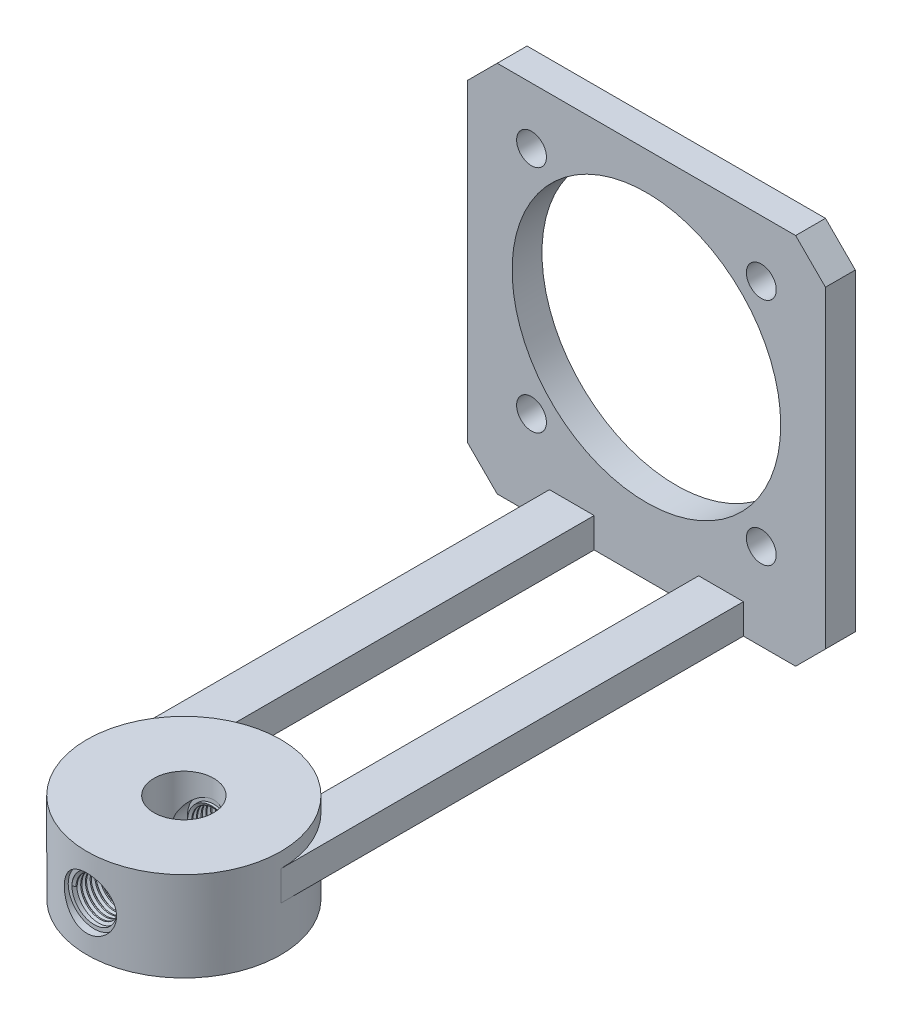
SolidWorks part; units mm, degrees
material "3.0205 (EN-AW 1200)"
ref_plane "前视基准面" through (0, 0, 0) normal (0, 0, 1) x (1, 0, 0)
ref_plane "上视基准面" through (0, 0, 0) normal (0, 1, 0) x (1, 0, 0)
ref_plane "右视基准面" through (0, 0, 0) normal (1, 0, 0) x (0, 0, -1)
sketch "草图1" plane through (0, 0, 0) normal (0, 1, 0) x (1, 0, 0)
  line L1 (5, 0) -> (2.5, 4.3301)
  line L2 (2.5, 4.3301) -> (-2.5, 4.3301)
  line L3 (-2.5, 4.3301) -> (-5, 0)
  line L4 (-5, 0) -> (-2.5, -4.3301)
  line L5 (-2.5, -4.3301) -> (2.5, -4.3301)
  line L6 (5, 0) -> (2.5, -4.3301)
sketch "草图2" plane through (0, 0, 0) normal (0, 1, 0) x (1, 0, 0)
  circle A0 centre (0, 0) radius 6.5
extrude "凸台-拉伸1" add sketch "草图2" along normal blind 2
sketch "草图3" plane through (0, 2, 0) normal (0, 1, 0) x (1, 0, 0)
  circle A0 centre (0, 0) radius 2
extrude "切除-拉伸2" cut sketch "草图3" against normal mid plane 10
sketch "草图4" plane through (0, 2, 0) normal (0, 1, 0) x (1, 0, 0)
  line L1 (6.5, 31) -> (3.8991, 31)
  line L3 (-6.5, 0) -> (-6.5, 31)
  line L4 (-6.5, 31) -> (-4.1009, 31)
  line L7 (-6.5, 0) -> (6.5, 0)
  line L8 (6.5, 0) -> (6.5, 31)
  line L11 (-4.1009, 31) -> (3.8991, 31)
  circle A0 centre (0, 0) radius 6.5 construction
  circle A1 centre (0, 0) radius 6.5
extrude "凸台-拉伸2" add sketch "草图4" against normal blind 2
sketch "草图6" plane through (0, 0, -31) normal (0, 0, -1) x (-1, 0, 0)
  line L5 (-15.5564, 5.1908) -> (-3.328, -1.1893)
sketch "草图18" plane through (0, 0, 0) normal (0, -1, 0) x (1, 0, 0)
  circle A0 centre (0, 0) radius 2.5328
sketch "草图20" plane through (0, 0, 0) normal (1, 0, 0) x (0, 0, -1)
  line L0 (0, 2) -> (0, 3)
  circle A0 centre (0, 3) radius 1.5
sketch "草图21" plane through (0, 0, -31) normal (0, 0, -1) x (-1, 0, 0)
  line L0 (0, 0) -> (12, 0)
  line L1 (12, 0) -> (12, 25)
  line L2 (12, 25) -> (-12, 25)
  line L3 (-12, 25) -> (-12, 0)
  line L4 (-12, 0) -> (0, 0)
extrude "凸台-拉伸3" add sketch "草图21" along normal blind 2
sketch "草图22" plane through (0, 0, -31) normal (0, 0, 1) x (1, 0, 0)
  line L0 (-6.5, 2) -> (-12, 2)
  line L1 (-12, 0) -> (-12, 25) construction
  line L2 (0, 2) -> (0, 25)
  line L3 (-6.5, 2) -> (6.5, 2) construction
  line L4 (-12, 25) -> (12, 25) construction
  line L5 (0, 13.5) -> (7.7, 13.5)
  line L6 (7.7, 13.5) -> (7.7, 21.2)
  line L7 (7.7, 21.2) -> (-7.7, 21.2)
  line L8 (-7.7, 21.2) -> (-7.7, 5.8)
  line L9 (-7.7, 5.8) -> (7.7, 5.8)
  circle A0 centre (0, 13.5) radius 9
  circle A1 centre (7.7, 21.2) radius 1
  circle A2 centre (-7.7, 21.2) radius 1
  circle A3 centre (-7.7, 5.8) radius 1
  circle A4 centre (7.7, 5.8) radius 1
extrude "切除-拉伸4" cut sketch "草图22" against normal blind 2 contours A0 | A3 | A4 | A1 | A2
chamfer "倒角1" distance 2 4 edges at (-12, 0, -32) (12, 0, -32) (12, 25, -32) (-12, 25, -32)
sketch "草图23" plane through (0, 0, 0) normal (0, -1, 0) x (1, 0, 0)
  line L0 (-6.5, 0) -> (-3.5, 0)
  line L1 (-3.5, 0) -> (-3.5, -31)
  line L2 (-3.5, -31) -> (3.5, -31)
  line L3 (3.5, -31) -> (3.5, 0)
  line L4 (3.5, 0) -> (6.5, 0)
  circle A0 centre (0, 0) radius 6.5
extrude "切除-拉伸5" cut sketch "草图23" against normal blind 10 contours A0 L1 L2 L3
sketch "草图24" plane through (0, 2, 0) normal (0, 1, 0) x (1, 0, 0)
  circle A0 centre (0, 0) radius 2
  circle A1 centre (0, 0) radius 6.5
sketch "草图26" plane through (0, 2, 0) normal (0, 1, 0) x (1, 0, 0)
  circle A0 centre (0, 0) radius 6.5
extrude "凸台-拉伸5" add sketch "草图26" along normal blind 1
sketch "草图27" plane through (0, 0, 0) normal (0, -1, 0) x (1, 0, 0)
  circle A0 centre (0, 0) radius 6.5
extrude "凸台-拉伸6" add sketch "草图27" along normal blind 3
sketch "草图28" plane through (0, -3, 0) normal (0, -1, 0) x (1, 0, 0)
  circle A0 centre (0, 0) radius 2
extrude "切除-拉伸7" cut sketch "草图28" against normal through all
sketch "草图29" plane through (0, 0, 0) normal (0, 0, 1) x (1, 0, 0)
  line L0 (0, 3) -> (0, -3)
  line L1 (6.5, 3) -> (-6.5, 3) construction
  line L2 (-6.5, -3) -> (6.5, -3) construction
  circle A0 centre (0, 0) radius 1.75
extrude "切除-拉伸8" cut sketch "草图29" against normal mid plane 4 contours A0
sketch "草图54" plane through (0, 0, -2) normal (0, 0, 1) x (1, 0, 0)
  circle A0 centre (0, 0) radius 1.5
extrude "切除-拉伸10" cut sketch "草图54" against normal blind 4
sketch "草图55" plane through (0, 0, -6) normal (0, 0, 1) x (1, 0, 0)
  circle A0 centre (0, 0) radius 1.75
extrude "切除-拉伸11" cut sketch "草图55" against normal blind 4
thread "螺纹线6" pitch 0.3175 start angle 0, offset 0, length 4, pitch 0.3175, diameter 3
ref_plane "基准面10" through (1.5, 0, -6) normal (0, -1, 0) x (1, 0, 0)
sketch "螺纹线轮廓10" plane through (1.5, 0, -6) normal (0, -1, 0) x (1, 0, 0)
  line L0 (0, 0) -> (0, 0.3175) construction
  line L11 (0, 0) -> (0, 0.2778)
  line L12 (0, 0.2778) -> (-0.1719, 0.1786)
  line L13 (-0.1719, 0.1786) -> (-0.1719, 0.0992)
  line L15 (-0.1719, 0.0992) -> (0, 0)
  line L17 (-0.1719, 0.1389) -> (0, 0.1389) construction
  point P2 (0, 0)
  dimension "Pitch" = 0.3175
  dimension "Profile_Angle" = 60
  dimension "Profile_Land" = 0.0794
  dimension "Profile_Height" = 0.1719
sketch "草图60" plane through (0, 0, 2) normal (0, 0, -1) x (-1, 0, 0)
  circle A0 centre (0, 0) radius 1.5
extrude "切除-拉伸12" cut sketch "草图60" against normal blind 4
sketch "草图61" plane through (0, 0, 6) normal (0, 0, -1) x (-1, 0, 0)
  circle A0 centre (0, 0) radius 1.75
extrude "切除-拉伸13" cut sketch "草图61" against normal blind 4
thread "螺纹线7" pitch 0.3175 profile "螺纹线轮廓11" start angle 0, offset 0, length 4, pitch 0.3175, diameter 3
ref_plane "基准面11" through (-1.5, 0, 6) normal (0, -1, 0) x (-1, 0, 0)
sketch "螺纹线轮廓11" plane through (-1.5, 0, 6) normal (0, -1, 0) x (-1, 0, 0)
  line L0 (0, 0) -> (0, 0.3175) construction
  line L11 (0, 0) -> (0, 0.2778)
  line L12 (0, 0.2778) -> (-0.1719, 0.1786)
  line L13 (-0.1719, 0.1786) -> (-0.1719, 0.0992)
  line L15 (-0.1719, 0.0992) -> (0, 0)
  line L17 (-0.1719, 0.1389) -> (0, 0.1389) construction
  point P2 (0, 0)
  dimension "Pitch" = 0.3175
  dimension "Profile_Angle" = 60
  dimension "Profile_Land" = 0.0794
  dimension "Profile_Height" = 0.1719
